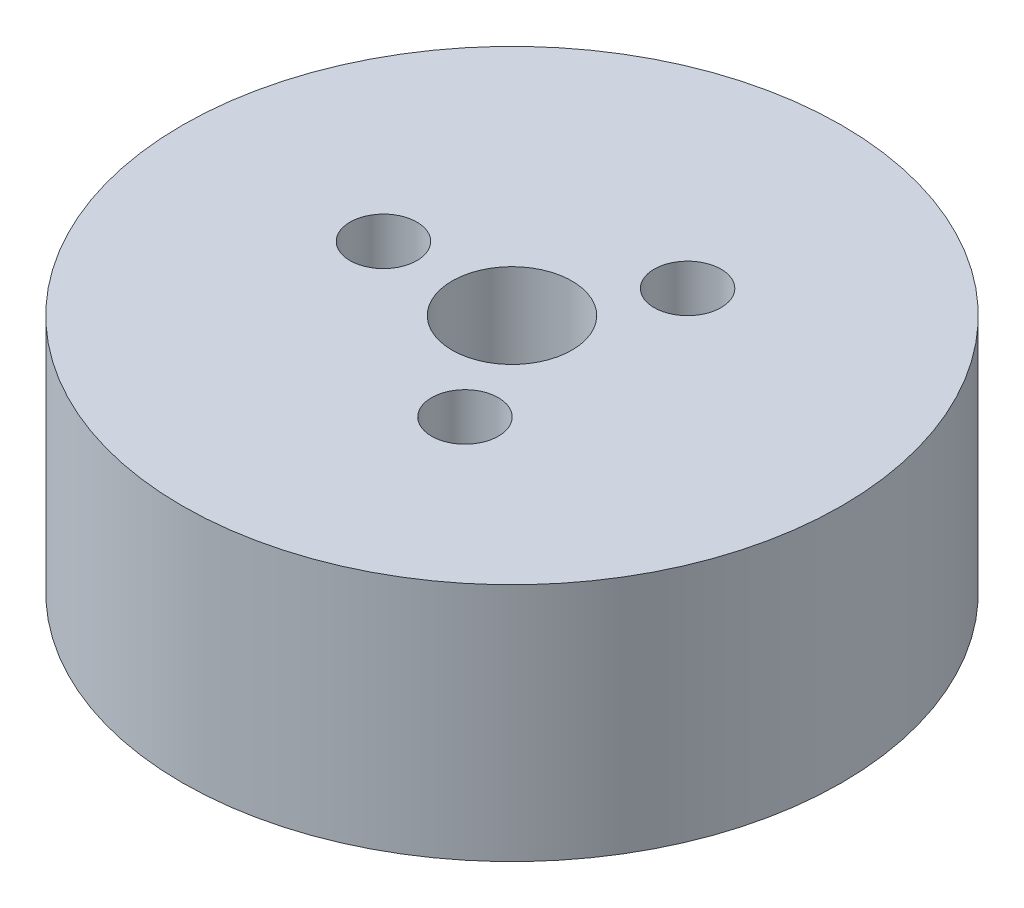
SolidWorks part; units mm, degrees
ref_plane "Front Plane" through (0, 0, 0) normal (0, 0, 1) x (1, 0, 0)
ref_plane "Top Plane" through (0, 0, 0) normal (0, 1, 0) x (1, 0, 0)
ref_plane "Right Plane" through (0, 0, 0) normal (1, 0, 0) x (0, 0, -1)
sketch "Sketch1" plane through (0, 0, 0) normal (0, 1, 0) x (1, 0, 0)
  circle A0 centre (0, 0) radius 27.5
  dimension "FLANGE_OD" = 55
extrude "Boss-Extrude1" add sketch "Sketch1" along normal blind 20
sketch "Sketch2" plane through (0, 0, 0) normal (0, 1, 0) x (1, 0, 0)
  circle A0 centre (0, 0) radius 5
  dimension "BORE_D" = 10
extrude "Cut-Extrude1" cut sketch "Sketch2" along normal through all
sketch "Sketch3" plane through (0, 20, 0) normal (0, 1, 0) x (1, 0, 0)
  circle A0 centre (0, 0) radius 10.7212 construction
  circle A1 centre (-10.7212, 0) radius 2.7876
  dimension "BOLT_D" = 5.5751
  dimension "BOLT_PCD" = 21.4424
extrude "Cut-Extrude2" cut sketch "Sketch3" against normal blind 16.9196
pattern_circular "CirPattern1" count 3 over 360 about axis through (0, 0, 0) along (0, 1, 0) of "Cut-Extrude2"
